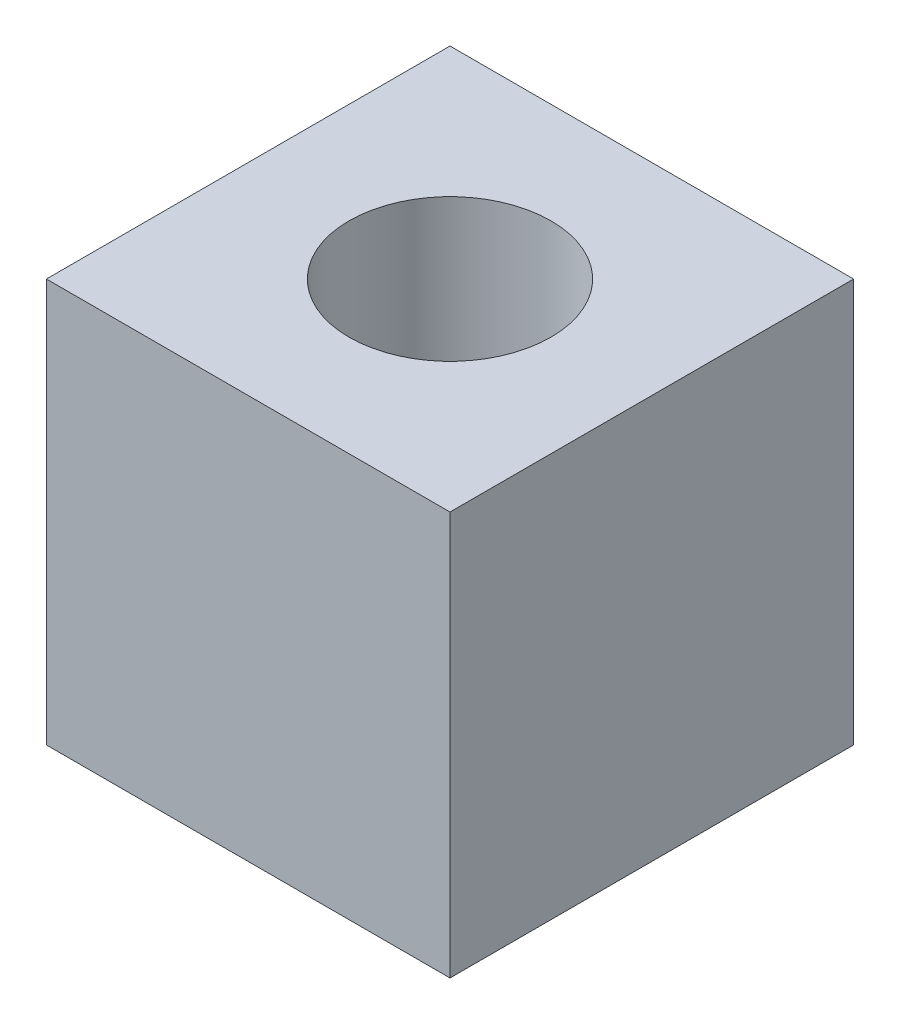
SolidWorks part; units mm, degrees
ref_plane "Front Plane" through (0, 0, 0) normal (0, 0, 1) x (1, 0, 0)
ref_plane "Top Plane" through (0, 0, 0) normal (0, 1, 0) x (1, 0, 0)
ref_plane "Right Plane" through (0, 0, 0) normal (1, 0, 0) x (0, 0, -1)
sketch "Sketch1" plane through (0, 0, 0) normal (0, 1, 0) x (1, 0, 0)
  line L1 (0, 0) -> (30, 0)
  line L2 (0, 0) -> (0, 30)
  line L3 (0, 30) -> (30, 30)
  line L4 (30, 0) -> (30, 30)
  dimension "D1" = 30
extrude "Boss-Extrude1" add sketch "Sketch1" along normal blind 30
sketch "Sketch2" plane through (0, 0, 0) normal (0, -1, 0) x (1, 0, 0)
  circle A0 centre (15, -15) radius 7.5
  dimension "D1" = 15
extrude "Cut-Extrude1" cut sketch "Sketch2" against normal blind 30
